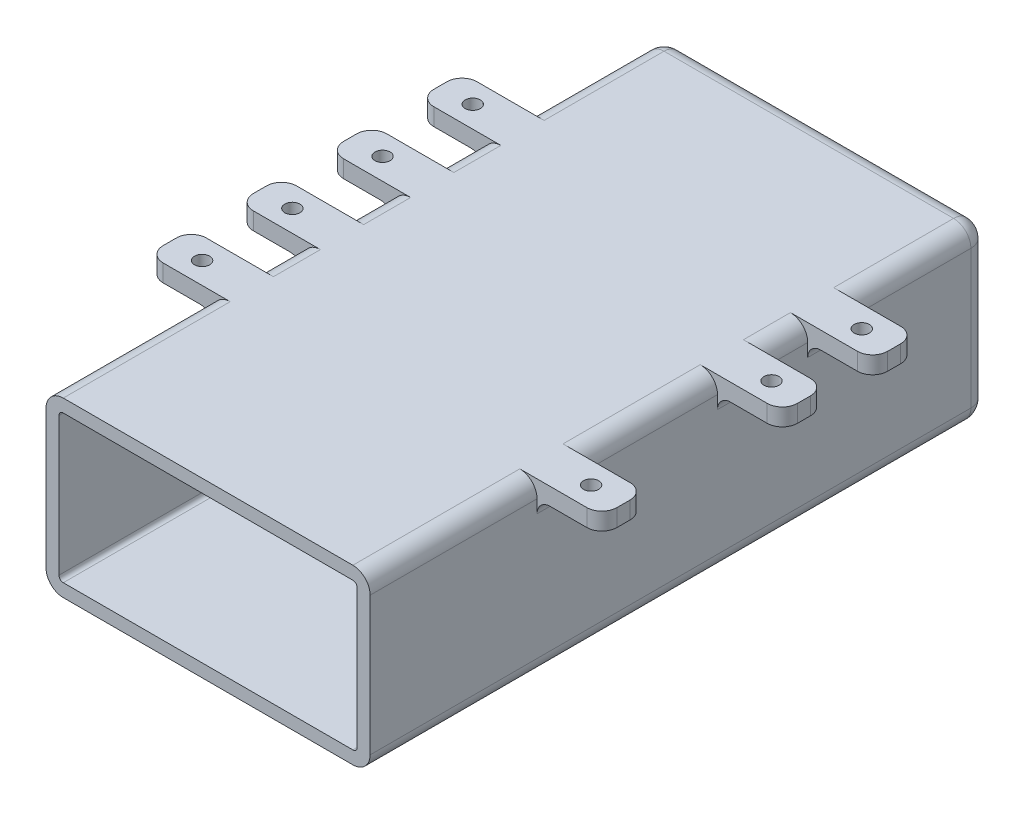
SolidWorks part; units mm, degrees
ref_plane "Plan de face" through (0, 0, 0) normal (0, 0, 1) x (1, 0, 0)
ref_plane "Plan de dessus" through (0, 0, 0) normal (0, 1, 0) x (1, 0, 0)
ref_plane "Plan de droite" through (0, 0, 0) normal (1, 0, 0) x (0, 0, -1)
sketch "Esquisse1" plane through (0, 0, 0) normal (0, 0, 1) x (1, 0, 0)
  line L1 (-34.5, 17) -> (34.5, 17)
  line L2 (-34.5, 17) -> (-34.5, -17)
  line L3 (-34.5, -17) -> (34.5, -17)
  line L4 (34.5, 17) -> (34.5, -17)
  point P5 (0, 17)
  point P7 (-34.5, 0)
  dimension "D1" = 34
  dimension "D2" = 69
extrude "Boss.-Extru.1" add sketch "Esquisse1" along normal blind 140
shell "Coque1" thickness 3 removed face at (0, 0, 140) outward yes
fillet "Congé3" radius 4 8 edges at (0, -20, -3) (37.5, 0, -3) (0, 20, -3) (-37.5, 0, -3) (-37.5, 20, 68.5) (-37.5, -20, 68.5) (37.5, -20, 68.5) (37.5, 20, 68.5)
sketch "Esquisse2" plane through (0, 20, 0) normal (0, 1, 0) x (1, 0, 0)
  line L0 (-33.5, -1) -> (-33.5, -140) construction
  line L1 (-33.5, -7.875) -> (-52.5, -7.875) construction
  line L2 (-33.5, -7.875) -> (-33.5, -17.875) construction
  line L3 (-33.5, -17.875) -> (-52.5, -17.875) construction
  line L4 (-52.5, -7.875) -> (-52.5, -17.875) construction
  line L5 (-37.5, -140) -> (-37.5, -1) construction
  line L6 (-33.5, -28.75) -> (-52.5, -28.75)
  line L7 (-33.5, -28.75) -> (-33.5, -38.75)
  line L8 (-33.5, -38.75) -> (-52.5, -38.75)
  line L9 (-52.5, -28.75) -> (-52.5, -38.75)
  line L10 (-33.5, -59.625) -> (-52.5, -59.625)
  line L11 (-33.5, -59.625) -> (-33.5, -49.625)
  line L12 (-33.5, -49.625) -> (-52.5, -49.625)
  line L13 (-52.5, -59.625) -> (-52.5, -49.625)
  line L14 (33.5, -70.5) -> (52.5, -70.5) construction
  line L15 (-52.5, -54.625) -> (-37.5, -54.625) construction
  line L16 (-43, -49.625) -> (-43, -38.75) construction
  line L17 (-43, -28.75) -> (-43, -17.875) construction
  line L18 (-43, -7.875) -> (-43, 3) construction
  line L19 (-43, 3) -> (0, 3) construction
  line L20 (-33.5, 3) -> (33.5, 3) construction
  line L21 (0, -1) -> (0, 3) construction
  line L22 (33.5, -1) -> (-33.5, -1) construction
  line L23 (52.5, -28.75) -> (52.5, -38.75)
  line L24 (33.5, -7.875) -> (52.5, -7.875) construction
  line L25 (52.5, -7.875) -> (52.5, -17.875) construction
  line L26 (33.5, -17.875) -> (52.5, -17.875) construction
  line L27 (33.5, -28.75) -> (52.5, -28.75)
  line L28 (33.5, -38.75) -> (52.5, -38.75)
  line L29 (33.5, -59.625) -> (52.5, -59.625)
  line L30 (52.5, -59.625) -> (52.5, -49.625)
  line L31 (33.5, -49.625) -> (52.5, -49.625)
  line L32 (-43, -59.625) -> (-43, -70.5) construction
  line L33 (-43, -70.5) -> (-33.5, -70.5) construction
  line L34 (-33.5, -70.5) -> (-52.5, -70.5)
  line L35 (-52.5, -80.5) -> (-52.5, -70.5)
  line L36 (-33.5, -80.5) -> (-52.5, -80.5)
  line L37 (-33.5, -91.375) -> (-52.5, -91.375)
  line L38 (-52.5, -101.375) -> (-52.5, -91.375)
  line L39 (-33.5, -101.375) -> (-52.5, -101.375)
  line L40 (-33.5, -112.25) -> (-52.5, -112.25) construction
  line L41 (-52.5, -122.25) -> (-52.5, -112.25) construction
  line L42 (-33.5, -122.25) -> (-52.5, -122.25) construction
  line L43 (33.5, -122.25) -> (52.5, -122.25) construction
  line L44 (52.5, -122.25) -> (52.5, -112.25) construction
  line L45 (33.5, -112.25) -> (52.5, -112.25) construction
  line L46 (33.5, -101.375) -> (52.5, -101.375)
  line L47 (52.5, -101.375) -> (52.5, -91.375)
  line L48 (33.5, -91.375) -> (52.5, -91.375)
  line L49 (33.5, -80.5) -> (52.5, -80.5) construction
  line L50 (52.5, -80.5) -> (52.5, -70.5) construction
  circle A0 centre (-45, -54.625) radius 1.75
  circle A1 centre (-45, -33.75) radius 1.75
  circle A2 centre (-45, -12.875) radius 1.75 construction
  circle A3 centre (45, -12.875) radius 1.75 construction
  circle A4 centre (45, -33.75) radius 1.75
  circle A5 centre (45, -54.625) radius 1.75
  circle A9 centre (-45, -75.5) radius 1.75
  circle A10 centre (-45, -96.375) radius 1.75
  circle A11 centre (-45, -117.25) radius 1.75 construction
  circle A12 centre (45, -117.25) radius 1.75 construction
  circle A13 centre (45, -96.375) radius 1.75
  circle A14 centre (45, -75.5) radius 1.75 construction
  point P25 (-45, -54.625)
  point P26 (-52.5, -54.625)
  point P28 (-52.5, -33.75)
  point P29 (-52.5, -12.875)
  line M17 (-33.5, -1) -> (-33.5, -140)
  line M19 (33.5, -140) -> (33.5, -1)
  dimension "D3" = 3.5
  dimension "D1" = 15
  dimension "D2" = 10
  dimension "D4" = 4
extrude "Boss.-Extru.2" add sketch "Esquisse2" against normal blind 4 contours L1 L4 L3 A2 M17 | L6 L9 L8 A1 M17 | L13 L10 L12 A0 M17 | L26 L25 L24 A3 M19 | L28 L23 L27 A4 M19 | L31 L29 L30 A5 M19 | L42 L40 L41 A11 M17 | L39 L37 L38 A10 M17 | L36 L34 L35 A9 M17 | L49 L50 L14 A14 M19 | L48 L46 L47 A13 M19 | L45 L43 L44 A12 M19 region at (-42.8933, 20, 33.75) region at (-42.8933, 20, 96.375) region at (-42.8933, 20, 75.5) region at (-42.8933, 20, 54.625) region at (42.8933, 20, 96.375) region at (42.8933, 20, 54.625) region at (42.8933, 20, 33.75)
fillet "Congé5" radius 3.5 14 edges at (52.5, 18, 28.75) (52.5, 18, 38.75) (52.5, 18, 49.625) (52.5, 18, 59.625) (-52.5, 18, 28.75) (-52.5, 18, 38.75) (-52.5, 18, 49.625) (-52.5, 18, 59.625) (52.5, 18, 91.375) (52.5, 18, 101.375) (-52.5, 18, 101.375) (-52.5, 18, 91.375) (-52.5, 18, 80.5) (-52.5, 18, 70.5)
extrude "Enlèv. mat.-Extru.1" cut sketch "Esquisse1<2>" along normal up to surface (140 mm away) up to face at (0, 0, 140)
sketch "Esquisse1<2>" plane through (0, 0, 0) normal (0, 0, 1) x (1, 0, 0) same geometry as "Esquisse1"
fillet "Congé4" radius 1 8 edges at (0, 17, 0) (34.5, 0, 0) (0, -17, 0) (-34.5, 0, 0) (-34.5, -17, 70) (34.5, -17, 70) (34.5, 17, 70) (-34.5, 17, 70)
fillet "Congé7" radius 3 7 edges at (37.5, 16, 33.75) (37.5, 16, 54.625) (37.5, 16, 96.375) (-37.5, 16, 75.5) (-37.5, 16, 33.75) (-37.5, 16, 54.625) (-37.5, 16, 96.375)
sketch "Esquisse3" plane through (0, 0, -3) normal (0, 0, -1) x (-1, 0, 0)
  line L0 (-30.5, 13) -> (-30.5, 16) construction
  line L3 (-30.5, 13) -> (30.5, 13)
  line L4 (-30.5, 13) -> (-30.5, -13)
  line L5 (-30.5, -13) -> (30.5, -13)
  line L6 (30.5, 13) -> (30.5, -13)
  line L7 (33.5, 16) -> (-33.5, 16) construction
  line L8 (-30.5, 13) -> (-33.5, 13) construction
  line L9 (-33.5, 16) -> (-33.5, -16) construction
  point P4 (0, -13)
  point P5 (-30.5, 0)
  dimension "D1" = 3
extrude "Enlèv. mat.-Extru.2" cut sketch "Esquisse3" against normal up to next
fillet "Congé8" radius 1 4 edges at (-30.5, 13, -1.5) (-30.5, -13, -1.5) (30.5, -13, -1.5) (30.5, 13, -1.5)
